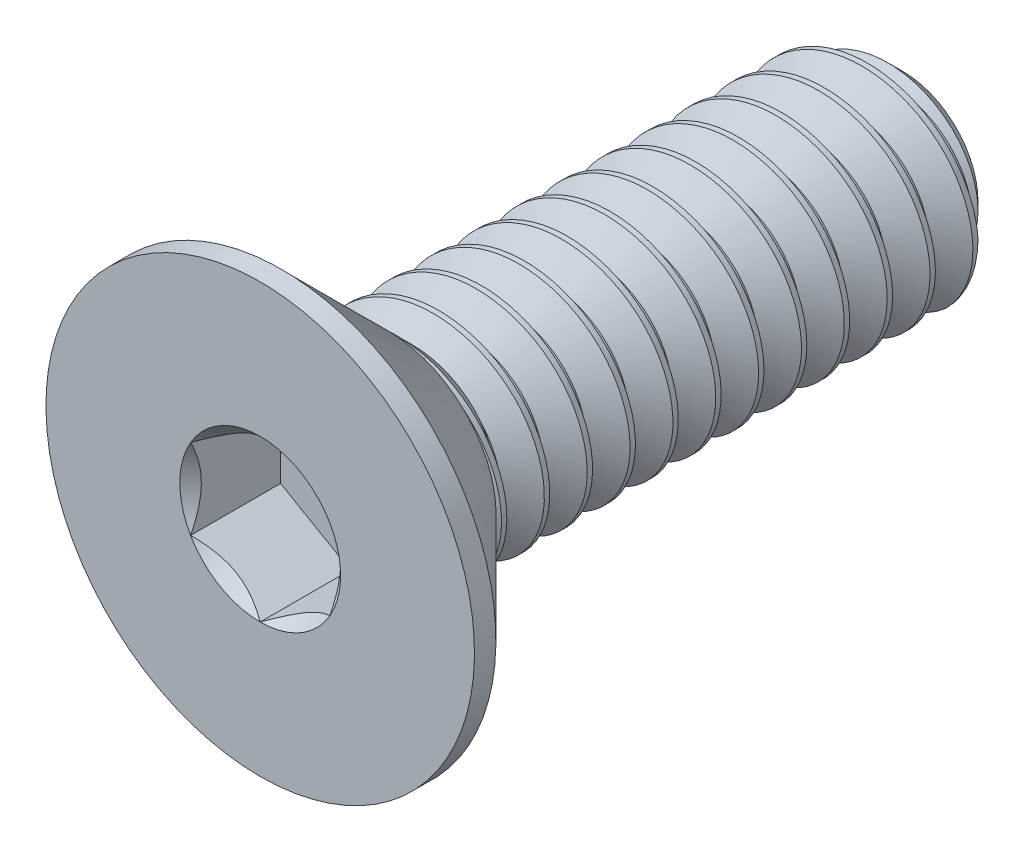
SolidWorks part; units mm, degrees
material "AISI Type 316L stainless steel"
ref_plane "Front" through (0, 0, 0) normal (0, 0, 1) x (1, 0, 0)
ref_plane "Top" through (0, 0, 0) normal (0, 1, 0) x (1, 0, 0)
ref_plane "Right" through (0, 0, 0) normal (1, 0, 0) x (0, 0, -1)
sketch "Sketch1" plane through (0, 0, 0) normal (1, 0, 0) x (0, 0, -1)
  line L0 (0, 2) -> (0.2, 2) construction
  line L1 (0.2, 2) -> (1.2, 1) construction
  line L2 (0, 1) -> (6, 1)
  line L3 (6, 1) -> (6, 0)
  line L4 (6, 0) -> (0, 0)
  line L5 (0, 0) -> (0, 2) construction
  line L6 (0, 2) -> (0, -2) construction
  line L7 (6, 1) -> (6, -1) construction
  line L8 (0, -2) -> (0.2, -2) construction
  line L9 (0.2, -2) -> (1.2, -1) construction
  line L11 (0, 1) -> (0, 0)
  line L12 (1.2, 1) -> (1.2, 0) construction
revolve "Revolve1" add sketch "Sketch1" angle 360 mid plane about L4
sketch "Sketch3" plane through (0, 0, -6) normal (0, 0, -1) x (-1, 0, 0)
  circle A0 centre (0, 0) radius 1
curve "Helix/Spiral1" pitch 0.4 height 6 radius 1 centre (0, 0, -6) axis (0, 0, 1) start towards (0, 1, 0)
sketch "Sketch2" plane through (0, 0, 0) normal (1, 0, 0) x (0, 0, -1)
  line L0 (6, 1) -> (6.35, 1)
  line L1 (6.35, 1) -> (6.2, 0.7402)
  line L2 (6.2, 0.7402) -> (6.15, 0.7402)
  line L3 (6.15, 0.7402) -> (6, 1)
  line L4 (6.075, 0.8701) -> (6.275, 0.8701) construction
  dimension "D1" = 60
  dimension "D2" = 0.05
  dimension "D3" = 0.2
chamfer "Chamfer1" distance 0.3 angle 45 1 edges at (0, 1, -6)
sweep "Cut-Sweep1" cut profiles "Sketch2" path "Helix/Spiral1" align with end faces yes
sketch "Sketch7" plane through (0, 0, 0) normal (1, 0, 0) x (0, 0, -1)
  line L0 (0, 2) -> (0.2, 2) construction
  line L1 (0.2, 2) -> (1.2, 1) construction
  line L2 (0, 2) -> (0.2, 2)
  line L3 (0.2, 2) -> (1.2, 1)
  line L4 (1.2, 1) -> (1.2, 0) construction
  line L5 (1.2, 1) -> (1.2, 0)
  line L7 (0, 0) -> (0, 2) construction
  line L8 (0, 0) -> (0, 2)
  line L9 (0, 0) -> (1.2, 0)
  line L10 (2.2, 0) -> (-2.2, 0) construction
revolve "Revolve2" add sketch "Sketch7" angle 360 mid plane about L9
ref_plane "Plane1" through (0, 0, -1.2) normal (0, 0, 1) x (1, 0, 0)
sketch "Sketch8" plane through (0, 0, -1.2) normal (0, 0, 1) x (1, 0, 0)
  circle A0 centre (0, 0) radius 1
extrude "Boss-Extrude1" add sketch "Sketch8" against normal through all draft 45
sketch "Sketch5" plane through (0, 0, 0) normal (0, 0, 1) x (1, 0, 0)
  line L1 (0.65, -0.3753) -> (0.65, 0.3753)
  line L2 (0.65, 0.3753) -> (0, 0.7506)
  line L3 (0, 0.7506) -> (-0.65, 0.3753)
  line L4 (-0.65, 0.3753) -> (-0.65, -0.3753)
  line L5 (-0.65, -0.3753) -> (0, -0.7506)
  line L6 (0, -0.7506) -> (0.65, -0.3753)
  circle A0 centre (0, 0) radius 0.65 construction
  dimension "Hex" = 1.3
extrude "Cut-Extrude2" cut sketch "Sketch5" against normal blind 0.84
sketch "Sketch6" plane through (0, 0, 0) normal (0, 0, 1) x (1, 0, 0)
  circle A0 centre (0, 0) radius 0.7506
extrude "Cut-Extrude3" cut sketch "Sketch6" against normal blind 0.84 draft 45
sketch "Sketch9" [suppressed] plane through (0, 0, -5.5) normal (0, 0, 1) x (1, 0, 0)
  circle A1 centre (0, 0) radius 5
  circle A2 centre (0, 0) radius 5
  point P0 (0, 5)
  dimension "D1" = 0
extrude "Boss-Extrude2" [suppressed] add sketch "Sketch9" against normal offset from surface (18.5 mm away) 26 up to face at (0, 0.7, -6)
fillet "Fillet1" [suppressed] radius 0.2
sketch "Sketch10" plane through (0, 0, 0) normal (1, 0, 0) x (0, 0, -1)
  line L0 (6, 1) -> (6, -1) construction
  point P0 (5.4, -1)
  dimension "D1" = 0.6
equation "\"D3@Helix/Spiral1\" = \"Lg@Sketch1\""
equation "\"D2@Sketch2\" = \"D4@Helix/Spiral1\" * .125"
equation "\"D3@Sketch2\" = \"D4@Helix/Spiral1\" * .5"
equation "\"D1@Chamfer1\" = \"D4@Helix/Spiral1\" * .75"
equation "\"D1@Cut-Extrude2\" = \"Head Ht@Sketch1\" * .7"
equation "\"D1@Sketch10\" = \"D4@Helix/Spiral1\" * 1.5"
equation "\"D1@Cut-Extrude3\" = \"D1@Cut-Extrude2\""
equation "\"D1@Fillet1\" = \"Dia@Sketch1\" * .1"
